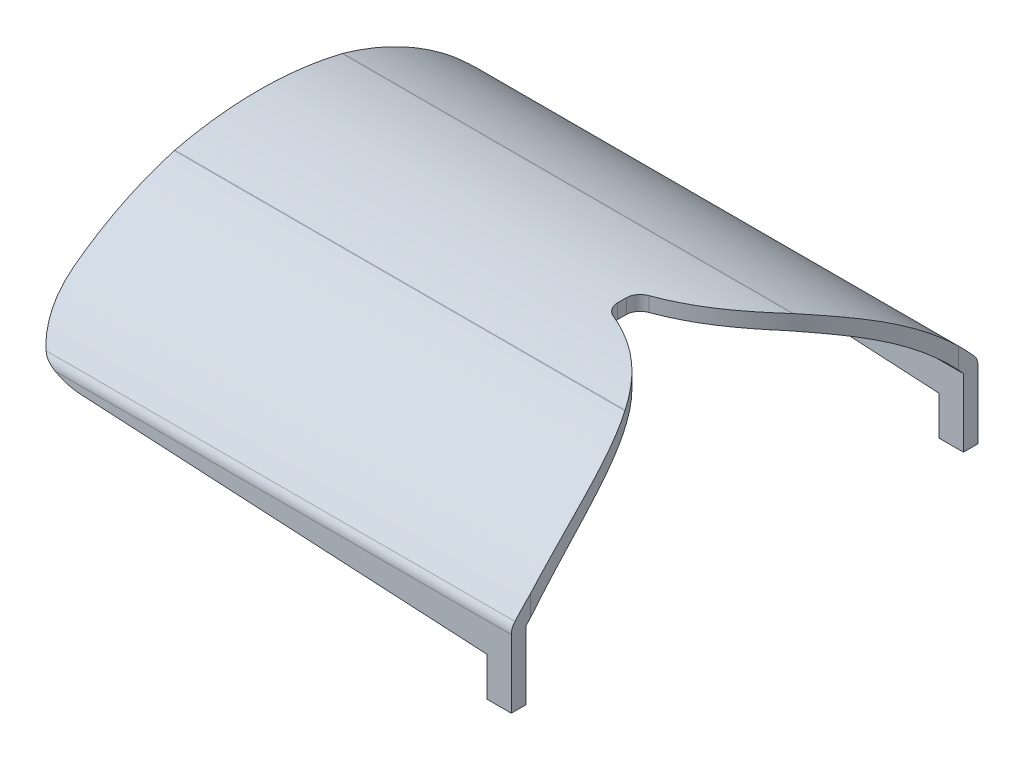
SolidWorks part; units mm, degrees
ref_plane "Front Plane" through (0, 0, 0) normal (0, 0, 1) x (1, 0, 0)
ref_plane "Top Plane" through (0, 0, 0) normal (0, 1, 0) x (1, 0, 0)
ref_plane "Right Plane" through (0, 0, 0) normal (1, 0, 0) x (0, 0, -1)
sketch "Sketch1" plane through (0, 0, 0) normal (1, 0, 0) x (0, 0, -1)
  line L1 (-45, -18) -> (-45, -32)
  line L2 (45, -18) -> (45, -32)
  arc A0 (-16.5013, 0) -> (-45, -18) centre (0, -57.6863) ccw
  arc A1 (16.5013, 0) -> (45, -18) centre (0, -57.6863) cw
  arc A2 (-16.5013, 0) -> (16.5013, 0) centre (0, -68.0272) cw
  dimension "D4" = 60
  dimension "D5" = 60
  dimension "D3" = 70
  dimension "D1" = 90
  dimension "D2" = 14
  dimension "D6" = 33.0027
  dimension "D7" = 28.4987
extrude "Extrude-Thin1" add sketch "Sketch1" along normal blind 100 thin thin type one direction wall 3
sketch "Sketch5" plane through (0, 0, 0) normal (0, 1, 0) x (1, 0, 0)
  line L0 (100, 17.2677) -> (100, 48) construction
  line L2 (74.7808, 3) -> (74.7808, -3)
  line L3 (-20.335, 0) -> (20.335, 0) construction
  line L4 (100, 44) -> (100, -44)
  spline S0 degree 2 poles (74.7808, 3) (97.6341, 10.563) (100, 44) knots 0 0 0 1 1 1
  spline S1 degree 2 poles (74.7808, -3) (97.6341, -10.563) (100, -44) knots 0 0 0 1 1 1
  point P4 (74.7808, 0)
  dimension "D1" = 3
extrude "Cut-Extrude2" cut sketch "Sketch5" against normal mid plane 67
fillet "Fillet1" radius 3 6 edges at (50, -16.8819, -48) (50, -16.8819, 48) (74.7808, 3.4098, 3) (74.7808, 3.4098, -3) (46.3282, 2.9011, -17.2677) (46.3282, 2.9011, 17.2677)
sketch "Sketch6" plane through (0, 0, -48) normal (0, 0, -1) x (-1, 0, 0)
  line L1 (-95, -24) -> (13.6709, -24)
  line L2 (-95, -24) -> (-95, -41.8798)
  line L3 (-95, -41.8798) -> (13.6709, -41.8798)
  line L4 (13.6709, -24) -> (13.6709, -41.8798)
  line L6 (-100, -32) -> (0, -32) construction
  line L7 (-100, -32) -> (-100, -18) construction
  dimension "D1" = 5
  dimension "D3" = 8
extrude "Cut-Extrude3" cut sketch "Sketch6" against normal blind 166
sketch "Sketch8" plane through (0, 0, 0) normal (0, 0, 1) x (1, 0, 0)
  line L0 (0, 1.9728) -> (-2.8489, -18)
  line L1 (100, -18) -> (0, -18) construction
  line L2 (-2.8489, -18) -> (7.1511, -18)
  line L3 (7.1511, -18) -> (15, 1.9728)
  line L4 (0, -18) -> (0, -24) construction
  line L5 (15, 1.9728) -> (0, 1.9728)
  dimension "D1" = 10
  dimension "D2" = 15
  dimension "D3" = 2.8489
extrude "Boss-Extrude1" add sketch "Sketch8" along normal mid plane 21 contours L3 L5 L0 L2
sketch "Sketch10" plane through (0, 0, 10.5) normal (0, 0, 1) x (1, 0, 0)
  line L0 (-2.8489, -18) -> (7.1511, -18) construction
  line L2 (-0.3489, -18) -> (3.9872, -18)
  arc A0 (-0.3489, -18) -> (3.9872, -18) centre (1.8191, -16.7552) cw
  dimension "D1" = 2.5
  dimension "D2" = 2.5
extrude "Cut-Extrude4" cut sketch "Sketch10" against normal blind 27 contours A0 L2
sketch "Sketch11" plane through (0, 0, -48) normal (0, 0, -1) x (-1, 0, 0)
  line L1 (0, -24) -> (-95, -24) construction
  line L2 (-100, -32) -> (-100, -18) construction
  circle A0 centre (-95, -19) radius 1.75
  dimension "D1" = 3.5
  dimension "D2" = 5
  dimension "D3" = 5
extrude "Cut-Extrude5" [suppressed] cut sketch "Sketch11" against normal blind 5
mirror "Mirror1" [suppressed] about plane through (0, 0, 0) normal (0, 0, 1)
sketch "Sketch12" plane through (0, 0, 0) normal (0, 0, 1) x (1, 0, 0)
  line L0 (74.7808, 1.9728) -> (74.7808, -15.9018)
  line L1 (74.7808, -15.9018) -> (83.2199, -15.9018)
  line L2 (83.2199, -15.9018) -> (83.2199, -19.5891)
  line L3 (83.2199, -19.5891) -> (67.6774, -19.5891)
  line L4 (67.6774, -19.5891) -> (67.6774, 1.9728)
  line L5 (74.7808, 1.9728) -> (15, 1.9728) construction
  line L6 (67.6774, 1.9728) -> (74.7808, 1.9728)
extrude "Boss-Extrude2" [suppressed] add sketch "Sketch12" along normal mid plane 15
sketch "Sketch13" [suppressed] plane through (74.7808, 0, 0) normal (1, 0, 0) x (0, 0, -1)
  line L0 (-7.5, -15.9018) -> (-7.5, 1.5698) construction
  line L2 (-7.5, 1.5698) -> (-7.5, -15.9018)
  line L3 (-7.5, -15.9018) -> (-3.705, -15.9018)
  line L4 (-3.705, 1.8746) -> (-3.705, -15.9018)
  line L5 (0, 20.5226) -> (0, -20.5226) construction
  line L6 (7.5, -15.9018) -> (3.705, -15.9018)
  line L7 (3.705, 1.8746) -> (3.705, -15.9018)
  line L9 (7.5, 1.5698) -> (7.5, -15.9018)
  line L10 (-7.5, -15.9018) -> (7.5, -15.9018) construction
  arc A0 (-0.8964, 1.967) -> (-7.5, 1.5698) centre (0, -68.0272) ccw construction
  arc A1 (-7.5, 1.5698) -> (-3.705, 1.8746) centre (0, -68.0272) cw
  arc A2 (3.705, 1.8746) -> (7.5, 1.5698) centre (0, -68.0272) cw
extrude "Cut-Extrude6" [suppressed] cut sketch "Sketch13" against normal blind 15
fillet "Fillet3" [suppressed] radius 2
sketch "Sketch15" plane through (0, 0, -48) normal (0, 0, -1) x (-1, 0, 0)
  line L0 (-95, -24) -> (0, -18.8601)
  line L1 (0, 20.5226) -> (0, -20.5226) construction
  line L2 (0, -18.8601) -> (0, -26.572)
  line L3 (0, -26.572) -> (-95, -24)
extrude "Cut-Extrude7" cut sketch "Sketch15" against normal blind 5
mirror "Mirror2" about plane through (0, 0, 0) normal (0, 0, 1) of "Cut-Extrude7"
fillet "Fillet5" radius 12 2 edges at (0, -18.8601, 46.5) (0, -18.8601, -46.5)
